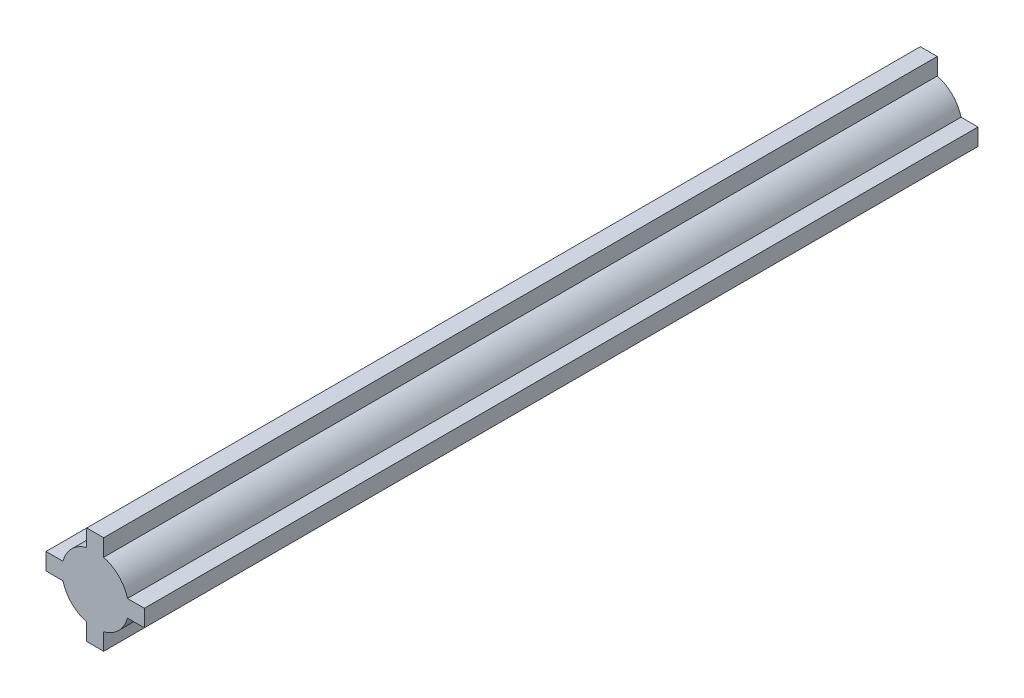
SolidWorks part; units mm, degrees
material "Alloy Steel"
ref_plane "Front Plane" through (0, 0, 0) normal (0, 0, 1) x (1, 0, 0)
ref_plane "Top Plane" through (0, 0, 0) normal (0, 1, 0) x (1, 0, 0)
ref_plane "Right Plane" through (0, 0, 0) normal (1, 0, 0) x (0, 0, -1)
sketch "Sketch1" plane through (0, 0, 0) normal (0, 0, 1) x (1, 0, 0)
  line L0 (-0.254, 0.9672) -> (0.254, 0.9672)
  line L1 (-0.254, 0.9672) -> (-0.254, 1.4752)
  line L2 (0.254, 0.9672) -> (0.254, 1.4752)
  line L3 (-0.254, 1.4752) -> (0.254, 1.4752)
  line L4 (-0.254, -0.9672) -> (0.254, -0.9672)
  line L5 (-0.254, -0.9672) -> (-0.254, -1.4752)
  line L6 (0.254, -0.9672) -> (0.254, -1.4752)
  line L7 (-0.254, -1.4752) -> (0.254, -1.4752)
  line L8 (0.9672, 0.254) -> (0.9672, -0.254)
  line L9 (0.9672, 0.254) -> (1.4752, 0.254)
  line L10 (0.9672, -0.254) -> (1.4752, -0.254)
  line L11 (1.4752, 0.254) -> (1.4752, -0.254)
  line L12 (-0.9672, 0.254) -> (-0.9672, -0.254)
  line L13 (-0.9672, 0.254) -> (-1.4752, 0.254)
  line L14 (-0.9672, -0.254) -> (-1.4752, -0.254)
  line L15 (-1.4752, 0.254) -> (-1.4752, -0.254)
  circle A0 centre (0, 0) radius 1
  dimension "D1" = 2
  dimension "D2" = 0.508
  dimension "D3" = 0.508
  dimension "D4" = 0.508
  dimension "D5" = 0.508
  dimension "D6" = 0.508
  dimension "D7" = 0.508
  dimension "D8" = 0.508
  dimension "D9" = 0.508
extrude "Boss-Extrude1" add sketch "Sketch1" along normal mid plane 25 contours L0 A0 | A0 L2 L3 L1 | L0 L2 L3 L1 | L15 L14 L12 L13 | L7 L6 L4 L5 | L11 L10 L8 L9 region at (0, 1.2321, 0) region at (0, 0, 0)
